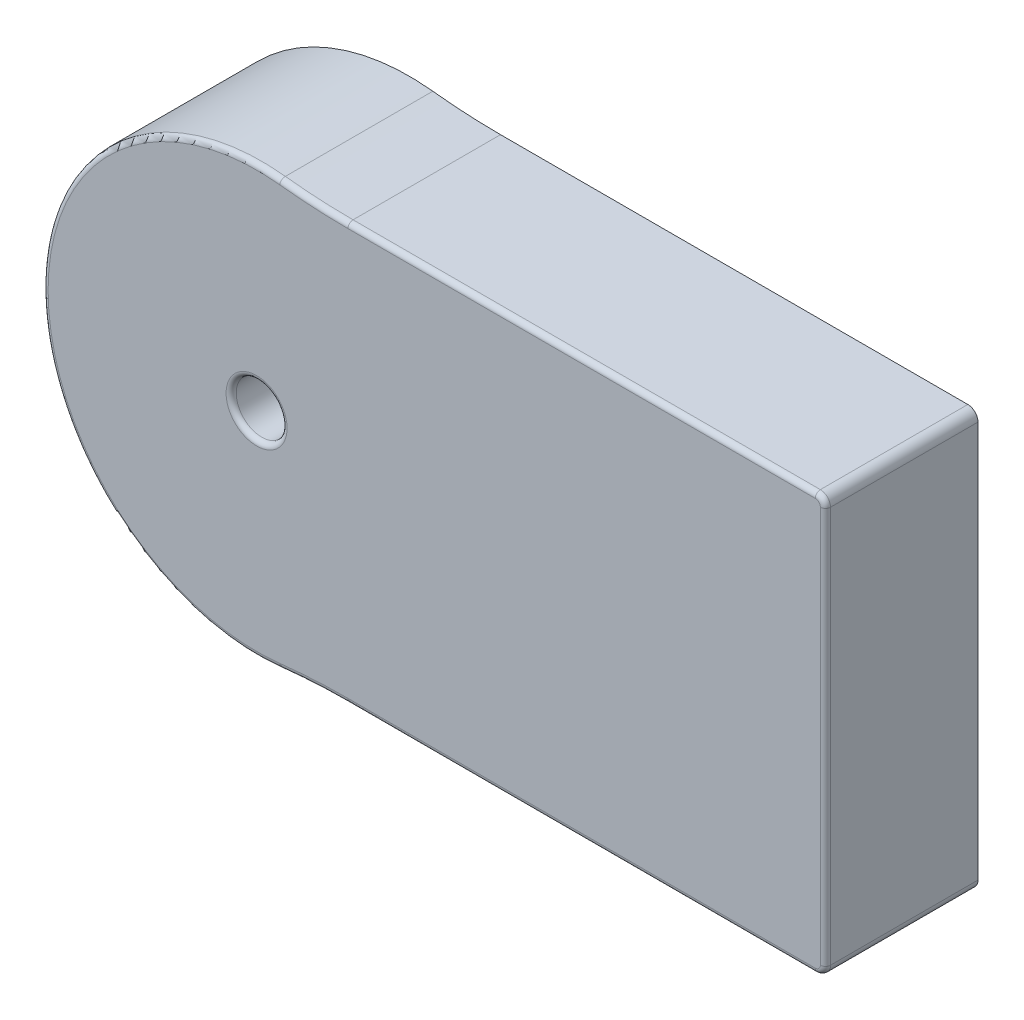
SolidWorks part; units mm, degrees
ref_plane "前视基准面" through (0, 0, 0) normal (0, 0, 1) x (1, 0, 0)
ref_plane "上视基准面" through (0, 0, 0) normal (0, 1, 0) x (1, 0, 0)
ref_plane "右视基准面" through (0, 0, 0) normal (1, 0, 0) x (0, 0, -1)
other "Configuration Table"
sketch "草图1" plane through (0, 0, 0) normal (0, 0, 1) x (1, 0, 0)
  line L1 (-20.9978, 38.2052) -> (99.9846, 38.2052)
  line L2 (-20.9978, 38.2052) -> (-20.9978, -43.7948)
  line L3 (-20.9978, -43.7948) -> (99.9846, -43.7948)
  line L4 (99.9846, 38.2052) -> (99.9846, -43.7948)
  circle A0 centre (-11.8874, -2.7948) radius 42
  circle A1 centre (-11.8874, -2.7948) radius 42 construction
  circle A2 centre (-11.8874, -2.7948) radius 5
  dimension "D1" = 82
extrude "凸台-拉伸1" add sketch "草图1" along normal blind 30 contours L1 A0 | L3 A0 L1 L2 | L2 A0 | L3 A0 | A0 L3 L4 L1 region at (-11.8874, 38.6056, 0) region at (1.5192, -2.7948, 0) region at (-34.7279, -2.7948, 0) region at (60.4109, -2.7948, 0) region at (-11.8874, -44.1952, 0)
fillet "圆角1" radius 120 2 edges at (-2.7769, 38.2052, 15) (-2.7769, -43.7948, 15)
fillet "圆角2" radius 1 1 edges at (-6.8874, -2.7948, 30)
fillet "圆角3" radius 1 6 edges at (-0.5818, 38.3905, 30) (53.0347, 38.2052, 30) (99.9846, -2.7948, 30) (-53.8874, -2.7948, 30) (53.0347, -43.7948, 30) (-0.5818, -43.9801, 30)
fillet "圆角4" radius 2 4 edges at (99.6917, -43.5019, 29.7071) (99.6917, 37.9123, 29.7071) (99.9846, 38.2052, 14.5) (99.9846, -43.7948, 14.5)
